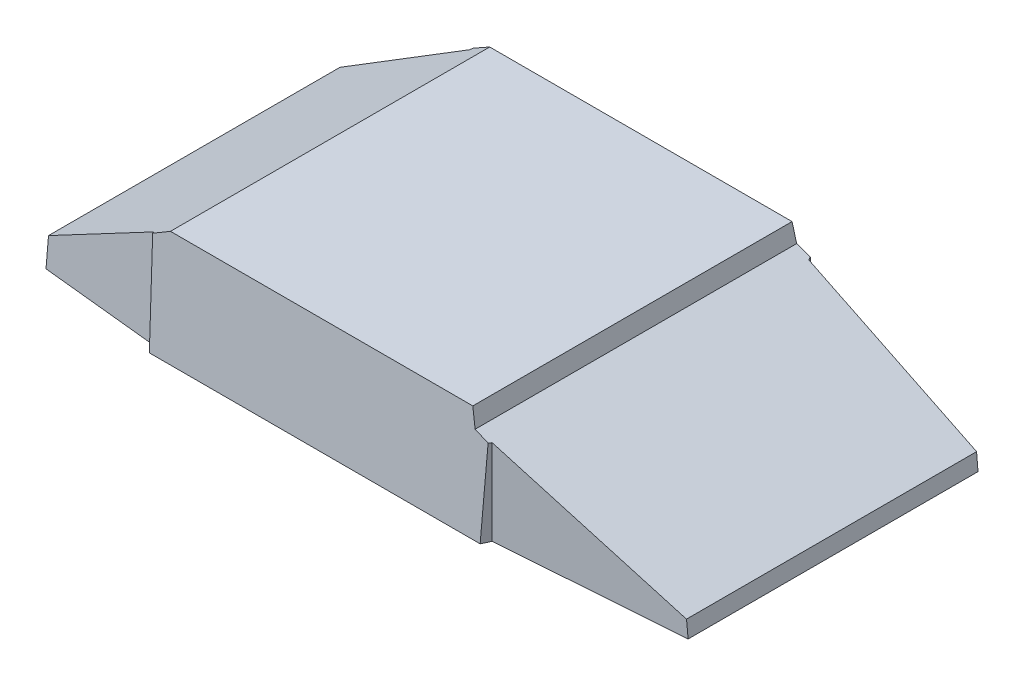
SolidWorks part; units mm, degrees
ref_plane "Front Plane" through (0, 0, 0) normal (0, 0, 1) x (1, 0, 0)
ref_plane "Top Plane" through (0, 0, 0) normal (0, 1, 0) x (1, 0, 0)
ref_plane "Right Plane" through (0, 0, 0) normal (1, 0, 0) x (0, 0, -1)
sketch "Sketch3" plane through (0, 0, 0) normal (0, 1, 0) x (1, 0, 0)
  line L1 (-180, 95) -> (180, 95)
  line L2 (-180, 95) -> (-180, -95)
  line L3 (-180, -95) -> (180, -95)
  line L4 (180, 95) -> (180, -95)
  line L5 (-180, 95) -> (180, -95) construction
  line L6 (-180, -95) -> (180, 95) construction
  point P0 (0, 0)
  dimension "D1" = 190
  dimension "D2" = 360
extrude "Boss-Extrude2" add sketch "Sketch3" along normal blind 158
sketch "Sketch4" plane through (180, 0, 0) normal (1, 0, 0) x (0, 0, -1)
  line L0 (-95, 0) -> (-95, 158)
  line L1 (-95, 158) -> (-85, 158)
  line L2 (-95, 158) -> (95, 158) construction
  line L3 (-85, 158) -> (-95, 0)
  line L4 (0, 0) -> (0, 123.75) construction
  line L5 (85, 158) -> (95, 0)
  line L6 (95, 158) -> (85, 158)
  line L7 (95, 0) -> (95, 158)
  dimension "D1" = 170
extrude "Cut-Extrude1" cut sketch "Sketch4" against normal through all
sketch "Sketch5" plane through (0, 0, 0) normal (0, 0, 1) x (1, 0, 0)
  line L0 (-180, 0) -> (-165.5, 158)
  line L1 (-180, 158) -> (180, 158) construction
  line L2 (-165.5, 158) -> (-180, 158)
  line L3 (-180, 158) -> (-180, 0)
  line L4 (0, 0) -> (0, 158) construction
  line L5 (180, 158) -> (180, 0)
  line L6 (165.5, 158) -> (180, 158)
  line L7 (180, 0) -> (165.5, 158)
  dimension "D1" = 331
extrude "Cut-Extrude2" cut sketch "Sketch5" against normal through all both and the other way through all
sketch "Sketch6" plane through (0, 0, 0) normal (0, 0, 1) x (1, 0, 0)
  line L0 (180, 0) -> (180, 105) construction
  line L2 (-165.5, 158) -> (165.5, 158) construction
  line L3 (65.8291, 148.4436) -> (180, 105)
  line L4 (180, 105) -> (180, 158)
  line L5 (-180, 110) -> (-180, 158)
  line L6 (-180, 158) -> (-97, 158)
  line L7 (-97, 158) -> (-180, 110)
  line L8 (-180, 0) -> (-180, 110) construction
  line L9 (65.8291, 148.4436) -> (64, 158)
  line L10 (64, 158) -> (180, 158)
  dimension "D1" = 105
  dimension "D2" = 110
  dimension "D3" = 83
  dimension "D4" = 116
extrude "Cut-Extrude3" cut sketch "Sketch6" along normal through all both and the other way through all
sketch "Sketch8" plane through (0, 0, 0) normal (0, 1, 0) x (1, 0, 0)
  line L0 (-180, 76.5) -> (-97, 85)
  line L3 (-180, 95) -> (-180, -95) construction
  line L4 (-180, 111.8161) -> (-180, 76.5)
  line L5 (0, 0) -> (-198.7212, 0) construction
  line L11 (-180, 111.8161) -> (-97, 111.8161)
  line L12 (-97, 111.8161) -> (-97, 85)
  line L13 (-97, -111.8161) -> (-97, -85)
  line L14 (-180, -111.8161) -> (-97, -111.8161)
  line L15 (-180, -111.8161) -> (-180, -76.5)
  line L16 (-180, -76.5) -> (-97, -85)
  line L17 (64, 85) -> (64, 140.1812)
  line L18 (64, 85) -> (180, 76.5)
  line L19 (180, 76.5) -> (197.104, 166.0233)
  line L20 (197.104, 166.0233) -> (64, 140.1812)
  line L21 (197.104, -166.0233) -> (64, -140.1812)
  line L22 (180, -76.5) -> (197.104, -166.0233)
  line L23 (64, -85) -> (180, -76.5)
  line L24 (64, -85) -> (64, -140.1812)
  line L29 (180, -95) -> (180, 95) construction
  dimension "D1" = 153
extrude "Cut-Extrude4" cut sketch "Sketch8" against normal through all and the other way through all
sketch "Sketch10" plane through (0, 0, 0) normal (0, -1, 0) x (1, 0, 0)
  line L1 (-156.5, -79) -> (156.5, -79) construction
  line L2 (-156.5, -79) -> (-156.5, 79) construction
  line L3 (-156.5, 79) -> (156.5, 79) construction
  line L4 (156.5, -79) -> (156.5, 79) construction
  line L5 (-156.5, -79) -> (156.5, 79) construction
  line L6 (-156.5, 79) -> (156.5, -79) construction
  point P0 (0, 0)
  dimension "D1" = 313
  dimension "D2" = 158
shell "Shell6" thickness 5 removed face at (-11, 0, 0)
sketch "Sketch11" plane through (0, 0, 0) normal (0, -1, 0) x (1, 0, 0)
  line L0 (-97, 95) -> (64, 95) construction
  line L1 (-97, 95) -> (64, 95)
  line L14 (-97, 95) -> (-97, 85)
  line L15 (-97, 85) -> (-180, 76.5)
  line L16 (-180, 76.5) -> (-180, -76.5)
  line L17 (-180, -76.5) -> (-97, -85)
  line L18 (-97, -85) -> (-97, -95)
  line L19 (-97, -95) -> (64, -95)
  line L20 (64, -95) -> (64, -85)
  line L21 (64, -85) -> (180, -76.5)
  line L22 (180, -76.5) -> (180, 76.5)
  line L23 (180, 76.5) -> (64, 85)
  line L24 (64, 85) -> (64, 95)
  line L25 (64, 95) -> (-97, 95)
  line L26 (-97, 95) -> (-97, 85)
  line L27 (-97, 85) -> (-180, 76.5)
  line L28 (-180, 76.5) -> (-180, -76.5)
  line L29 (-180, -76.5) -> (-97, -85)
  line L30 (-97, -85) -> (-97, -95)
  line L31 (-97, -95) -> (64, -95)
  line L32 (64, -95) -> (64, -85)
  line L33 (64, -85) -> (180, -76.5)
  line L34 (180, -76.5) -> (180, 76.5)
  line L35 (180, 76.5) -> (64, 85)
  line L36 (64, 85) -> (64, 95)
  line L37 (64, 95) -> (-97, 95)
  line M25 (-92, 80.4859) -> (-92, 89.99)
  line M26 (-92, 89.99) -> (59, 89.99)
  line M27 (59, 89.99) -> (59, 80.353)
  line M28 (59, 80.353) -> (174.979, 71.8545)
  line M29 (174.979, 71.8545) -> (174.979, -71.8545)
  line M30 (174.979, -71.8545) -> (59, -80.353)
  line M31 (59, -80.353) -> (59, -89.99)
  line M32 (59, -89.99) -> (-92, -89.99)
  line M33 (-92, -89.99) -> (-92, -80.4859)
  line M34 (-92, -80.4859) -> (-174.979, -71.988)
  line M35 (-174.979, -71.988) -> (-174.979, 71.988)
  line M36 (-174.979, 71.988) -> (-92, 80.4859)
  dimension "D1" = 0
extrude "Boss-Extrude3" add sketch "Sketch11" against normal blind 5 contours M25 M36 M35 M34 M33 M32 M31 M30 M29 M28 M27 M26 region at (-1.4169, 0, 0)
sketch "Sketch16" plane through (0, 5, 0) normal (0, 1, 0) x (1, 0, 0)
  line L0 (0, 0) -> (100, 0) construction
  line L1 (20, -41) -> (180, -41) construction
  line L2 (20, -41) -> (20, 41) construction
  line L3 (20, 41) -> (180, 41) construction
  line L4 (180, -41) -> (180, 41) construction
  line L5 (20, -41) -> (180, 41) construction
  line L6 (20, 41) -> (180, -41) construction
  line L7 (180, -76.5) -> (180, 76.5) construction
  line L8 (61.8177, -49) -> (123.6355, -49)
  line L9 (61.8177, 41) -> (123.6355, 41)
  line L10 (61.8177, 41) -> (61.8177, 49)
  line L11 (61.8177, 49) -> (123.6355, 49)
  line L12 (123.6355, 41) -> (123.6355, 49)
  line L13 (123.6355, -41) -> (123.6355, -49)
  line L14 (61.8177, -41) -> (123.6355, -41)
  line L15 (61.8177, -41) -> (61.8177, -49)
  line L17 (20, 17.0174) -> (12, 17.0174)
  line L18 (20, 17.0174) -> (20, -8.6402)
  line L19 (20, -8.6402) -> (12, -8.6402)
  line L20 (12, 17.0174) -> (12, -8.6402)
  point P0 (100, 0)
  dimension "D1" = 82
  dimension "D2" = 160
  dimension "D3" = 8
  dimension "D4" = 8
extrude "Boss-Extrude4" add sketch "Sketch16" along normal blind 17.5
chamfer "Chamfer1" distance 19.9 angle 25 2 edges at (-97, 79, -85) (64, 79, 85) first distance on face at (-97, 52.6667, -88.3333) first distance on face at (64, 52.6667, 88.3333)
chamfer "Chamfer2" distance 19.9 angle 25 2 edges at (-97, 79, 85) (64, 79, -85) first distance on face at (-97, 52.6667, 88.3333) first distance on face at (64, 52.6667, -88.3333)
sketch "Sketch17" plane through (0, 0, 0) normal (0, 0, 1) x (1, 0, 0)
  line L0 (-156.5, 0) -> (156.5, 0) construction
  line L1 (-208.8748, 100) -> (247.2709, 100)
  line L2 (-208.8748, 100) -> (-208.8748, 0)
  line L3 (-208.8748, 0) -> (247.2709, 0)
  line L4 (247.2709, 100) -> (247.2709, 0)
  point P4 (0, 0)
  dimension "D1" = 100
extrude "Cut-Extrude5" cut sketch "Sketch17" against normal through all both and the other way through all
